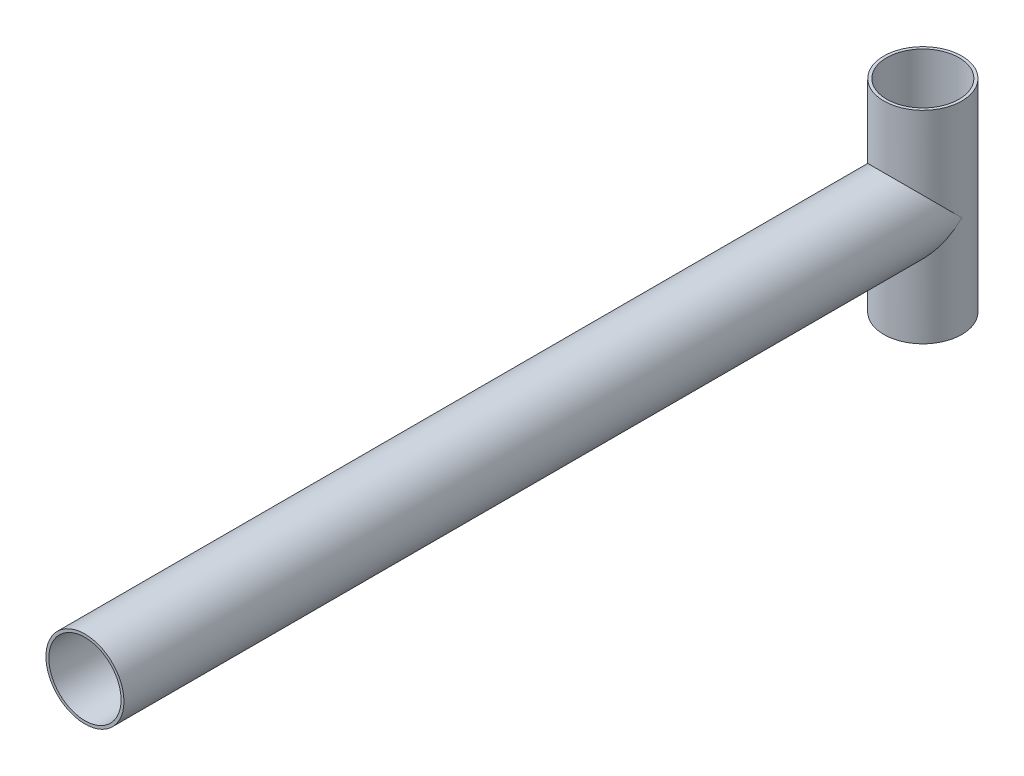
SolidWorks part; units mm, degrees
ref_plane "Front Plane" through (0, 0, 0) normal (0, 0, 1) x (1, 0, 0)
ref_plane "Top Plane" through (0, 0, 0) normal (0, 1, 0) x (1, 0, 0)
ref_plane "Right Plane" through (0, 0, 0) normal (1, 0, 0) x (0, 0, -1)
sketch "Sketch1" plane through (0, 0, 0) normal (0, 1, 0) x (1, 0, 0)
  circle A0 centre (0, 0) radius 13.5
  dimension "D1" = 27
extrude "Boss-Extrude1" add sketch "Sketch1" along normal mid plane 70
sketch "Sketch2" plane through (0, 0, 0) normal (0, 0, 1) x (1, 0, 0)
  circle A0 centre (0, 0) radius 13.5
  dimension "D1" = 27
extrude "Boss-Extrude2" add sketch "Sketch2" along normal blind 290
shell "Shell1" thickness 1 removed face at (0, -35, 13.5) removed face at (0, 35, 13.5) removed face at (13.5, 0, 290)
